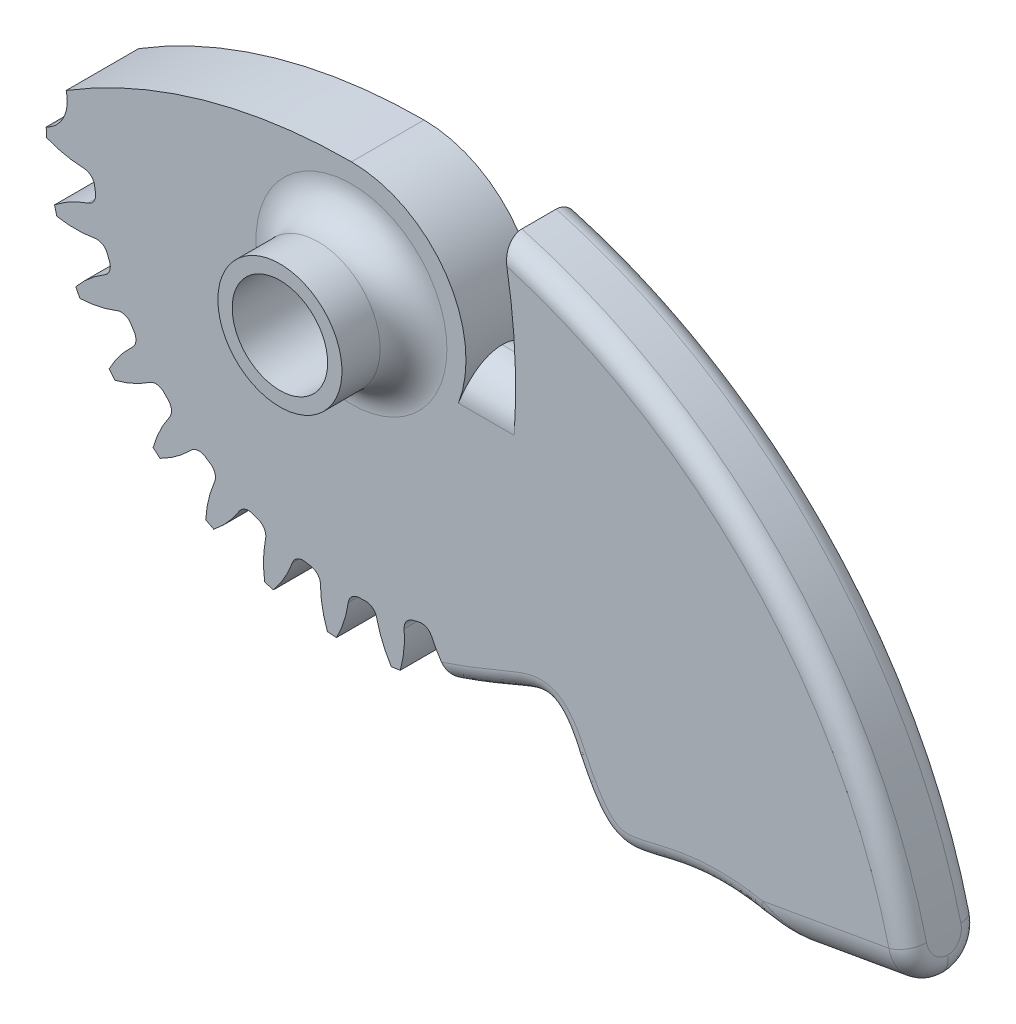
SolidWorks part; units mm, degrees
material "ABS"
ref_plane "Front" through (0, 0, 0) normal (0, 0, 1) x (1, 0, 0)
ref_plane "Top" through (0, 0, 0) normal (0, 1, 0) x (1, 0, 0)
ref_plane "Right" through (0, 0, 0) normal (1, 0, 0) x (0, 0, -1)
sketch "Sketch3" plane through (0, 0, 0) normal (0, 0, 1) x (1, 0, 0)
  circle A0 centre (0, 0) radius 40.64
  dimension "od" = 40.64
extrude "gearBody" add sketch "Sketch3" along normal blind 9.652
sketch "Sketch2" plane through (0, 0, 0) normal (0, 0, 1) x (1, 0, 0)
  line L0 (0, 0) -> (34.0786, 14.1158) construction
  line L1 (45.4751, -11.4855) -> (0, 0) construction
  line L2 (0, 0) -> (36.3143, 0) construction
  line L3 (38.0972, -0.458) -> (37.8451, -4.4001) construction
  line L5 (37.9712, -2.4291) -> (0, 0) construction
  line L7 (0, 0) -> (36.8864, 0) construction
  arc A0 (36.879, -0.7403) -> (36.6727, -3.9649) centre (0, 0) ccw construction
  arc A1 (40.637, 0.4947) -> (40.2427, -5.6687) centre (0, 0) ccw construction
  arc A2 (38.0972, -0.458) -> (37.8451, -4.4001) centre (0, 0) ccw construction
  arc A3 (34.9015, -2.6404) -> (34.9534, -1.8283) centre (0, 0) ccw construction
  arc A4 (45.4751, -11.4855) -> (35.6466, -3.6712) centre (32.0022, -18.3431) ccw construction
  arc A5 (45.4751, -11.4855) -> (46.5679, 5.5974) centre (0, 0) ccw construction
  arc A6 (46.5679, 5.5974) -> (35.8238, -0.9008) centre (34.0786, 14.1158) cw construction
  arc A7 (34.9534, -1.8283) -> (35.8238, -0.9008) centre (35.9376, -1.8798) cw construction
  arc A8 (35.6466, -3.6712) -> (34.9015, -2.6404) centre (35.8842, -2.7147) cw construction
  arc A9 (46.8801, 7.0756) -> (35.7652, -0.3962) centre (34.0786, 14.1158) cw
  arc A10 (34.4461, -1.8018) -> (35.7652, -0.3962) centre (35.9376, -1.8798) cw
  arc A11 (34.3949, -2.6021) -> (34.4461, -1.8018) centre (0, 0) ccw
  arc A12 (35.5241, -4.1642) -> (34.3949, -2.6021) centre (35.8842, -2.7147) cw
  arc A13 (45.5964, -12.9914) -> (35.5241, -4.1642) centre (32.0022, -18.3431) ccw
  arc A14 (45.5964, -12.9914) -> (46.8801, 7.0756) centre (0, 0) ccw
  point P6 (46.5679, 5.5974)
  point P22 (45.4751, -11.4855)
  dimension "D1" = 0.508
  dimension "baseDia" = 73.7729
  dimension "od" = 81.28
  dimension "pd" = 76.2
  dimension "rd" = 70.0024
  dimension "rFillet" = 0.9855
  dimension "pointX" = 46.5679
  dimension "pointY" = 5.5974
  dimension "CTT" = 3.9421
  dimension "flankCenterAngle" = 22.5
extrude "toothCut" cut sketch "Sketch2" along normal through all
pattern_circular "CirPattern1" count 30 over 360 about axis through (0, 0, 9.652) along (0, 0, -1) of "toothCut"
sketch "hub1Dia" plane through (0, 0, 0) normal (0, 0, -1) x (-1, 0, 0)
  circle A0 centre (0, 0) radius 12.7
  dimension "hub1Dia" = 25.4
sketch "hub2Dia" plane through (0, 0, 9.652) normal (0, 0, 1) x (1, 0, 0)
  circle A0 centre (0, 0) radius 12.7
  dimension "hub2dia" = 25.4
sketch "boreDia" plane through (0, 0, 0) normal (0, 0, 1) x (1, 0, 0)
  circle A0 centre (0, 0) radius 6.7469
  dimension "boreDia" = 13.4937
extrude "bore" cut sketch "boreDia" against normal mid plane 25400
sketch "Sketch4" plane through (0, 0, 9.652) normal (0, 0, 1) x (1, 0, 0)
  circle A0 centre (0, -57.15) radius 76.1746
  arc A2 (-41.7195, 6.5842) -> (41.7195, 6.5842) centre (0, 0) cw
  dimension "D1" = 152.3492
  dimension "D2" = 57.15
extrude "Cut-Extrude1" cut sketch "Sketch4" against normal through all contours A0 region at (0, 26.0638, 9.652)
sketch "Sketch5" plane through (0, 0, 9.652) normal (0, 0, 1) x (1, 0, 0)
  line L0 (0, 19.0246) -> (21.5163, 3.7176)
  line L1 (21.5163, 3.7176) -> (10.4433, -33.7781)
  line L2 (10.4433, -33.7781) -> (13.558, -38.3117)
  line L3 (0, 0) -> (0, -57.15) construction
  line L4 (0, -57.15) -> (-54.1615, -3.586) construction
  line L5 (0, -57.15) -> (65.9691, -95.2373) construction
  line L9 (0, -57.15) -> (75.0173, -43.9224) construction
  line L12 (60.232, -46.5295) -> (75.0173, -43.9224)
  line L13 (0, -57.15) -> (29.696, -40.005) construction
  line L14 (29.696, -40.005) -> (26.521, -34.5057) construction
  circle A1 centre (0, -57.15) radius 76.1746 construction
  arc A5 (0, 19.0246) -> (75.0173, -43.9224) centre (0, -57.15) cw
  circle A6 centre (0, -57.15) radius 21.59 construction
  arc A9 (10.6752, -34.1372) -> (8.9309, -33.317) centre (9.3176, -34.7596) ccw construction
  circle A12 centre (49.4934, -85.725) radius 40.64 construction
  spline S0 degree 3 poles (13.558, -38.3117) (21.087, -35.7646) (26.3659, -31.8249) (36.3578, -56.1686) (39.5345, -39.0169) (60.232, -46.5295) knots 0 0 0 0 0.118515 0.218515 1 1 1 1
  point P28 (21.569, -56.1981)
  dimension "D1" = 43.18
  dimension "D3" = 81.28
  dimension "D6" = 152.3492
  dimension "D2" = 120
  dimension "D4" = 57.15
  dimension "D8" = 57.15
  dimension "D7" = 60
  dimension "D9" = 34.29
  dimension "D10" = 6.35
  dimension "D5" = 80
extrude "Boss-Extrude1" add sketch "Sketch5" against normal up to surface (9.652 mm away) up to face at (6.7469, 0, 0)
sketch "Sketch6" plane through (0, 0, 9.652) normal (0, 0, 1) x (1, 0, 0)
  line L1 (-41.2993, 3.0747) -> (-42.3397, 6.1739)
  line L2 (15.875, 0) -> (21.209, 0)
  circle A0 centre (0, -57.15) radius 76.1746 construction
  arc A1 (75.0173, -43.9224) -> (-33.55, 11.2383) centre (0, -57.15) ccw construction
  circle A2 centre (0, 0) radius 15.875 construction
  arc A3 (0, 15.875) -> (15.875, 0) centre (0, 0) cw
  arc A4 (19.4523, 16.499) -> (-42.3397, 6.1739) centre (0, -57.15) ccw
  arc A5 (0, 15.875) -> (-41.2993, 3.0747) centre (0, -57.15) ccw
  circle A6 centre (0, 0) radius 21.209 construction
  circle A8 centre (-57.15, 0) radius 78.359 construction
  arc A9 (21.209, 0) -> (19.4523, 16.499) centre (-57.15, 0) ccw
  dimension "D4" = 57.15
  dimension "D1" = 31.75
  dimension "D2" = 42.418
  dimension "D3" = 156.718
extrude "Cut-Extrude2" cut sketch "Sketch6" against normal through all
sketch "Sketch7" plane through (0, 0, 9.652) normal (0, 0, 1) x (1, 0, 0)
  circle A0 centre (0, 0) radius 6.7469
  circle A1 centre (0, 0) radius 6.7469 construction
  circle A2 centre (0, 0) radius 8.255
  dimension "D1" = 16.51
extrude "spacer" add sketch "Sketch7" along normal blind 9.525
fillet "Fillet1" radius 4.445 1 edges at (8.255, 0, 9.652)
sketch "Sketch8" plane through (0, 0, 9.652) normal (0, 0, 1) x (1, 0, 0)
  line L0 (-38.1756, 5.1017) -> (-34.0224, 5.3247)
  line L1 (-34.0224, 5.3247) -> (-34.2899, 0.0545)
  line L2 (-34.2899, 0.0545) -> (-40.6263, -1.0555)
  arc A0 (-38.1756, 5.1017) -> (-40.6263, -1.0555) centre (-42.6187, 3.3039) cw
extrude "overextension stop" add sketch "Sketch8" against normal up to surface (9.652 mm away) up to face at (-13.508, -22.4485, 0)
sketch "Sketch11" plane through (0, 0, 9.652) normal (0, 0, 1) x (1, 0, 0)
  line L3 (15.2268, -0.635) -> (21.8414, -0.635)
  line L4 (15.2268, -0.635) -> (21.8414, -0.635)
  line L6 (-37.9725, 4.4812) -> (-39.287, 5.4618)
  line L7 (-39.287, 5.4618) -> (-10.5387, 26.6943)
  line L8 (-10.5387, 26.6943) -> (20.0731, 16.6327)
  arc A5 (-40.3928, -0.941) -> (-38.1756, 5.1017) centre (-42.6187, 3.3039) ccw construction
  arc A6 (15.2268, -0.635) -> (0, 15.24) centre (0, 0) ccw
  arc A7 (21.8414, -0.635) -> (20.0731, 16.6327) centre (-57.15, 0) ccw
  arc A8 (15.2268, -0.635) -> (0, 15.24) centre (0, 0) ccw
  arc A9 (21.8414, -0.635) -> (20.0731, 16.6327) centre (-57.15, 0) ccw
  arc A10 (0, 15.24) -> (-37.8436, 4.5604) centre (0, -57.15) ccw
  arc A11 (0, 15.24) -> (-37.9725, 4.4812) centre (0, -57.15) ccw
  dimension "D1" = 0.635
  dimension "D2" = 0.635
extrude "Cut-Extrude3" cut sketch "Sketch11" against normal through all
sketch "Sketch10" plane through (0, 0, 9.652) normal (0, 0, 1) x (1, 0, 0)
  circle A0 centre (0, 0) radius 6.35
  circle A1 centre (0, 0) radius 7.3025
  dimension "D1" = 12.7
  dimension "D2" = 14.605
extrude "bore dia" add sketch "Sketch10" along normal up to surface and the other way up to surface up to face at (8.255, 0, 19.177) other way up to face at (-12.6074, -23.7153, 0)
fillet "Fillet4" radius 4.826 4 edges at (18.5341, -0.635, 0) (18.5341, -0.635, 9.652) (67.6247, -45.2259, 0) (67.6247, -45.2259, 9.652)
fillet "Fillet3" radius 2.286 4 edges at (56.6479, -45.3986, 8.5331) (54.7143, -44.9405, 0.585)
fillet "Fillet5" radius 2.54 4 edges at (54.6564, -4.0911, 0) (74.8265, -42.8823, 1.8113) (74.6811, -42.1399, 8.5966) (54.6564, -4.0911, 9.652)
equation "\"Bodytube_OD\" = 6.17in"
equation "\"Bodytube_ID\" = 5.998in"
equation "\"Fwd_Tube_Length\" = 40in"
equation "\"Mid_Tube_Length\"= 1in"
equation "\"Aft_Section_Length\"= 39in"
equation "\"Mid_Coupler_Length\"= 13in"
equation "\"Aft_Lower_Length\"= 22in"
equation "\"AB_Coupler_OD_Length\"= 1in"
equation "\"AB_Coupling_Section_Length\"= 0.375in"
equation "\"AB_Coupler_Length\"= \"AB_Coupler_OD_Length\" + \"AB_Coupling_Section_Length\" * 2"
equation "\"Cutout_Angle\" = 80"
equation "\"AB_Paddle_Height\" = 0.375in"
equation "\"AB_Coupler_Num_Screws\"= 4"
equation "\"Num_Cutouts\" = 3"
equation "\"AB_Coupler_OD\"= 6.17in"
equation "\"AB_Coupler_ID\"= 5.75in"
equation "\"AB_Coupler_Surface_Diameter\"= 5.998in"
equation "\"AB_Coupling_Screw_Diameter\"= 0.15748in"
equation "\"AB_Central_Bushing_Length\" = .4724in"
equation "\"Lead_Screw_Dist\" = 3.4in"
equation "\"Lead_Screw_Diam\" = 0.386in"
equation "\"Lead_Screw_Length\" = (\"Mid_Coupler_Length\" + 2*0.375in + 2*0.5in)"
equation "\"Paddle_Pin_Offset\" = .25in"
equation "\"Paddle_Pin_Radius\" = 2.25in"
equation "\"Fwd_BKHD_From_Top\" = 18in"
equation "\"D1@Sketch4\"=\"Bodytube_ID\""
equation "\"D2@Sketch4\"=\"Paddle_Pin_Radius\""
equation "\"D3@Sketch5\"=\"Paddle_Gear_OD\""
equation "\"D4@Sketch5\"=\"Paddle_Pin_Radius\""
equation "\"Motor_OD\" = 4in"
equation "\"Aft_Upper_Length\"= \"Aft_Section_Length\" - \"Aft_Lower_Length\" - \"AB_Coupler_OD_Length\""
equation "\"Paddle_Gear_OD\" = 3.2in"
equation "\"D5@Sketch5\"=\"Cutout_Angle\""
equation "\"D6@Sketch5\"=\"Bodytube_ID\""
equation "\"D1@Sketch6\"=\"AB_Coupler_ID\"-2*\"Paddle_Pin_Radius\""
equation "\"D2@Sketch6\"=\"Bodytube_OD\"-2*\"Paddle_Pin_Radius\""
equation "\"D3@Sketch6\"=\"Bodytube_OD\""
equation "\"D4@Sketch6\"=\"Paddle_Pin_Radius\""
equation "\"D8@Sketch5\"=\"Paddle_Pin_Radius\""
equation "\"Drive_Gear_OD\" = 1.7in"
equation "\"Fin_Thickness\"= .118in"
equation "\"Guiderail_Cutout_Diameter\"= 1.5in"
equation "\"DB9_Hole_Dist\" = 25mm"
equation "\"D1@Sketch5\"=\"Drive_Gear_OD\""
